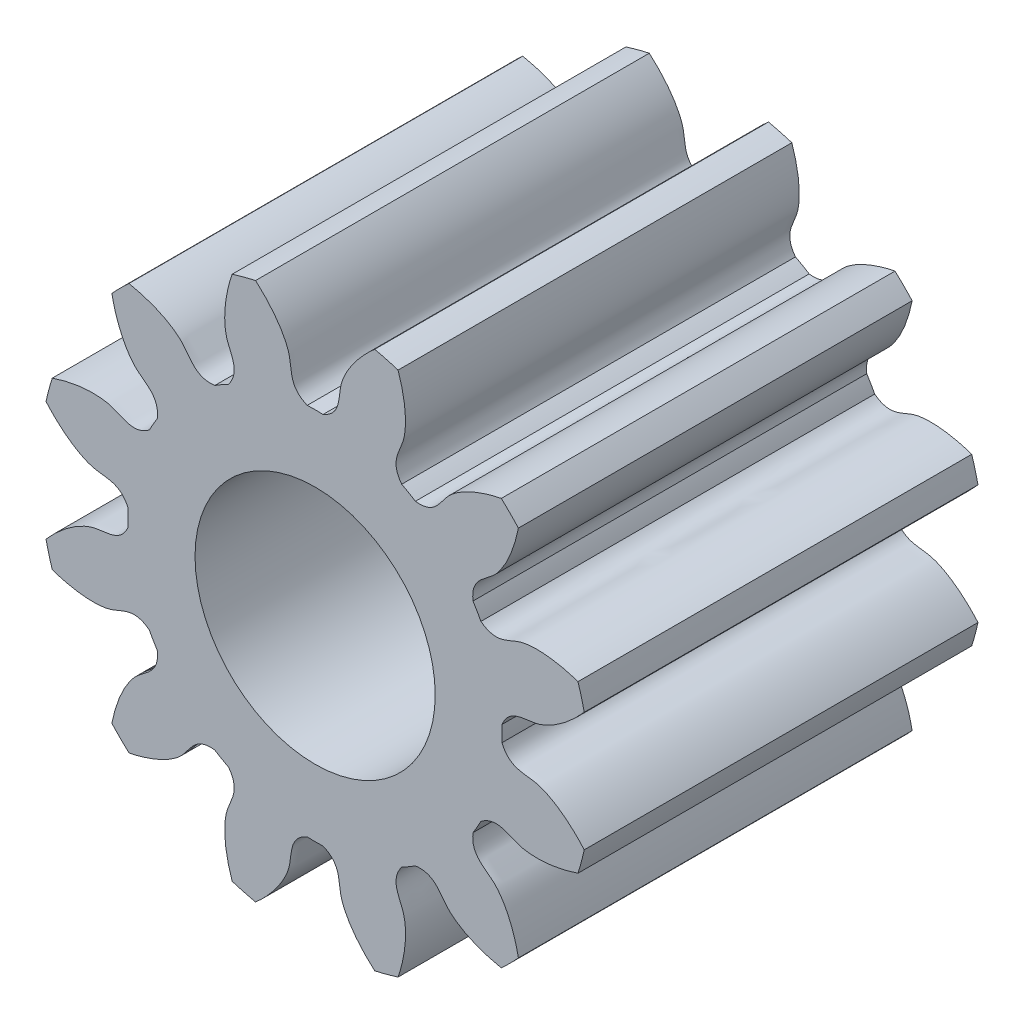
SolidWorks part; units mm, degrees
ref_plane "前视基准面" through (0, 0, 0) normal (0, 0, 1) x (1, 0, 0)
ref_plane "上视基准面" through (0, 0, 0) normal (0, 1, 0) x (1, 0, 0)
ref_plane "右视基准面" through (0, 0, 0) normal (1, 0, 0) x (0, 0, -1)
other "Configuration Table"
sketch "草图1" plane through (0, 0, 0) normal (0, 0, 1) x (1, 0, 0)
  circle A0 centre (0, 0) radius 3.5
extrude "凸台-拉伸1" add sketch "草图1" along normal blind 5
ref_axis "基准轴1" through (0, 0, 5) along (0, 0, -1)
sketch "草图2" plane through (0, 0, 0) normal (0, 0, 1) x (1, 0, 0)
  line L0 (0, 0) -> (0, 3.5) construction
  circle A0 centre (0, 0) radius 3.5 construction
  arc A1 (0.1004, 2.3729) -> (-0.1004, 2.3729) centre (0, 0) ccw
  arc A2 (1.7488, 3.9475) -> (-1.7488, 3.9475) centre (0, 0) ccw
  spline S0 degree 3 poles (0.1004, 2.3729) (0.3404, 2.4747) (0.2872, 2.6724) (0.3381, 2.8447) (0.3413, 2.855) (0.3451, 2.8662) (0.3495, 2.8784) (0.3546, 2.8915) (0.3603, 2.9056) (0.3668, 2.9206) (0.374, 2.9366) (0.3821, 2.9533) (0.3909, 2.971) (0.4007, 2.9894) (0.4114, 3.0086) (0.423, 3.0286) (0.4356, 3.0493) (0.4492, 3.0707) (0.4639, 3.0928) (0.4796, 3.1155) (0.4965, 3.1388) (0.5145, 3.1626) (0.5337, 3.187) (0.554, 3.2119) (0.5756, 3.2372) (0.5985, 3.2629) (0.6226, 3.289) (0.648, 3.3154) (0.6748, 3.342) (0.7028, 3.369) (0.7323, 3.3961) (0.7631, 3.4234) (0.7954, 3.4507) (0.829, 3.4782) (0.8641, 3.5057) (0.9006, 3.5331) (0.9385, 3.5604) (0.978, 3.5877) (1.0189, 3.6147) (1.0613, 3.6416) (1.1052, 3.6681) (1.1506, 3.6944) (1.1975, 3.7203) (1.2459, 3.7457) (1.2958, 3.7707) (1.3472, 3.7952) (1.4001, 3.8191) (1.4546, 3.8424) (1.5105, 3.865) (1.5679, 3.8869) (1.6472, 3.9154) (1.7078, 3.9351) (1.7488, 3.9475) knots 0 0 0 0 0.218015 0.222044 0.226546 0.231522 0.236972 0.242897 0.249295 0.256167 0.263513 0.271332 0.279626 0.288394 0.297636 0.307351 0.317541 0.328204 0.339341 0.350953 0.363038 0.375597 0.38863 0.402137 0.416118 0.430573 0.445502 0.460904 0.476781 0.493132 0.509956 0.527255 0.545027 0.563273 0.581994 0.601188 0.620856 0.640998 0.661614 0.682704 0.704268 0.726305 0.748817 0.771803 0.795262 0.819196 0.843603 0.868484 0.89384 0.919669 0.945972 1 1 1 1
  spline S1 degree 3 poles (-0.1004, 2.3729) (-0.3404, 2.4747) (-0.2872, 2.6724) (-0.3381, 2.8447) (-0.3413, 2.855) (-0.3451, 2.8662) (-0.3495, 2.8784) (-0.3546, 2.8915) (-0.3603, 2.9056) (-0.3668, 2.9206) (-0.374, 2.9366) (-0.3821, 2.9533) (-0.3909, 2.971) (-0.4007, 2.9894) (-0.4114, 3.0086) (-0.423, 3.0286) (-0.4356, 3.0493) (-0.4492, 3.0707) (-0.4639, 3.0928) (-0.4796, 3.1155) (-0.4965, 3.1388) (-0.5145, 3.1626) (-0.5337, 3.187) (-0.554, 3.2119) (-0.5756, 3.2372) (-0.5985, 3.2629) (-0.6226, 3.289) (-0.648, 3.3154) (-0.6748, 3.342) (-0.7028, 3.369) (-0.7323, 3.3961) (-0.7631, 3.4234) (-0.7954, 3.4507) (-0.829, 3.4782) (-0.8641, 3.5057) (-0.9006, 3.5331) (-0.9385, 3.5604) (-0.978, 3.5877) (-1.0189, 3.6147) (-1.0613, 3.6416) (-1.1052, 3.6681) (-1.1506, 3.6944) (-1.1975, 3.7203) (-1.2459, 3.7457) (-1.2958, 3.7707) (-1.3472, 3.7952) (-1.4001, 3.8191) (-1.4546, 3.8424) (-1.5105, 3.865) (-1.5679, 3.8869) (-1.6472, 3.9154) (-1.7078, 3.9351) (-1.7488, 3.9475) knots 0 0 0 0 0.218015 0.222044 0.226546 0.231522 0.236972 0.242897 0.249295 0.256167 0.263513 0.271332 0.279626 0.288394 0.297636 0.307351 0.317541 0.328204 0.339341 0.350953 0.363038 0.375597 0.38863 0.402137 0.416118 0.430573 0.445502 0.460904 0.476781 0.493132 0.509956 0.527255 0.545027 0.563273 0.581994 0.601188 0.620856 0.640998 0.661614 0.682704 0.704268 0.726305 0.748817 0.771803 0.795262 0.819196 0.843603 0.868484 0.89384 0.919669 0.945972 1 1 1 1
extrude "切除-拉伸1" cut sketch "草图2" along normal through all
pattern_circular "阵列(圆周)1" count 12 over 360 about axis through (0, 0, 5) along (0, 0, -1) of "切除-拉伸1"
sketch "草图3" plane through (0, 0, 0) normal (0, 0, 1) x (1, 0, 0)
  circle A0 centre (0, 0) radius 3 construction
  dimension "Dn" = 6
sketch "草图4" plane through (0, 0, 0) normal (0, 0, -1) x (-1, 0, 0)
  circle A0 centre (0, 0) radius 1.525
  dimension "D1" = 3.05
extrude "切除-拉伸2" cut sketch "草图4" against normal up to next
